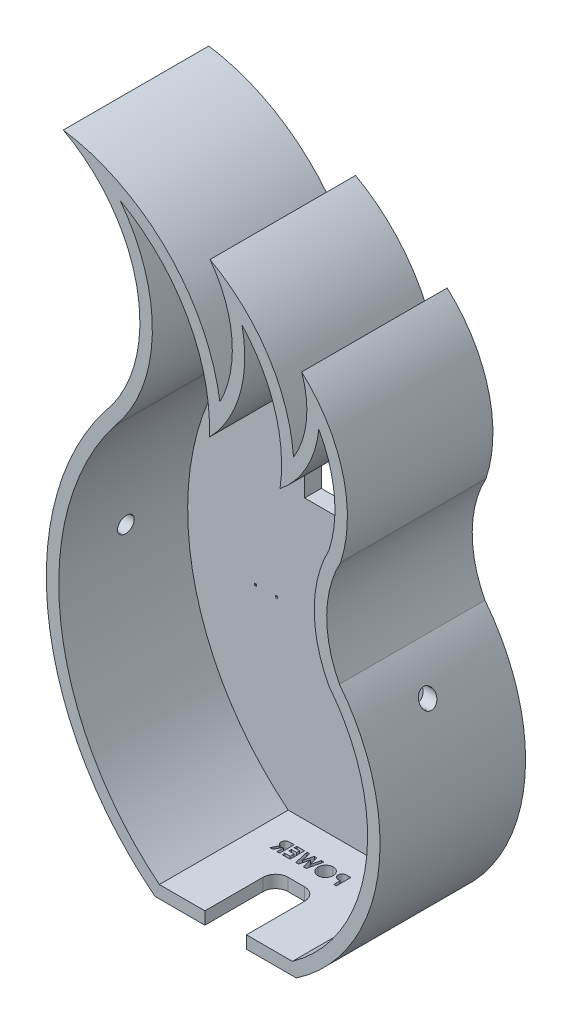
SolidWorks part; units mm, degrees
ref_plane "Plan de face" through (0, 0, 0) normal (0, 0, 1) x (1, 0, 0)
ref_plane "Plan de dessus" through (0, 0, 0) normal (0, 1, 0) x (1, 0, 0)
ref_plane "Plan de droite" through (0, 0, 0) normal (1, 0, 0) x (0, 0, -1)
sketch "Esquisse1" plane through (0, 0, 0) normal (0, 0, 1) x (1, 0, 0)
  line L11 (34.5922, -83.2059) -> (2.5922, -83.2059)
  arc A27 (-8.2284, 6.8779) -> (-6.8432, 54.5989) centre (-37.0902, 31.5963) ccw
  arc A28 (14.6078, 15.9991) -> (-6.8432, 54.5989) centre (-27.3471, 17.9439) ccw
  arc A29 (14.6078, 15.9991) -> (22.4562, 43.331) centre (-6.8587, 36.956) ccw
  arc A30 (31.6225, 13.7941) -> (22.4562, 43.331) centre (-4.0097, 18.927) ccw
  arc A31 (31.6225, 13.7941) -> (40.9447, 30.8086) centre (16.0766, 33.3728) ccw
  arc A32 (43.4046, 6.8505) -> (40.9447, 30.8086) centre (14.6078, 15.9991) ccw
  arc A33 (43.4046, 6.8505) -> (43.3898, -21.4623) centre (69.8471, -7.3198) ccw
  arc A34 (-8.2284, 6.8779) -> (2.5922, -83.2059) centre (43.4002, -32.6124) ccw
  arc A35 (34.5922, -83.2059) -> (43.3898, -21.4623) centre (9.6799, -48.1577) ccw
  point P0 (0, 0)
extrude "Boss.-Extru.1" add sketch "Esquisse1" along normal blind 4
sketch "Esquisse3" plane through (0, 0, 0) normal (0, 0, 1) x (1, 0, 0)
  line L1 (2.5922, -83.2059) -> (34.5922, -83.2059)
  line L2 (2.5922, -83.2059) -> (34.5922, -83.2059)
  line L4 (1.5465, -86.2059) -> (35.5321, -86.2059)
  line L5 (1.5465, -86.2059) -> (35.5321, -86.2059)
  arc A9 (-8.2284, 6.8779) -> (2.5922, -83.2059) centre (43.4002, -32.6124) ccw
  arc A10 (34.5922, -83.2059) -> (43.3898, -21.4623) centre (9.6799, -48.1577) ccw
  arc A11 (43.4046, 6.8505) -> (43.3898, -21.4623) centre (69.8471, -7.3198) ccw
  arc A12 (43.4046, 6.8505) -> (40.9447, 30.8086) centre (14.6078, 15.9991) ccw
  arc A13 (31.6225, 13.7941) -> (40.9447, 30.8086) centre (16.0766, 33.3728) ccw
  arc A14 (31.6225, 13.7941) -> (22.4562, 43.331) centre (-4.0097, 18.927) ccw
  arc A15 (14.6078, 15.9991) -> (22.4562, 43.331) centre (-6.8587, 36.956) ccw
  arc A16 (14.6078, 15.9991) -> (-6.8432, 54.5989) centre (-27.3471, 17.9439) ccw
  arc A17 (-8.2284, 6.8779) -> (-6.8432, 54.5989) centre (-37.0902, 31.5963) ccw
  arc A18 (-8.2284, 6.8779) -> (2.5922, -83.2059) centre (43.4002, -32.6124) ccw
  arc A19 (34.5922, -83.2059) -> (43.3898, -21.4623) centre (9.6799, -48.1577) ccw
  arc A20 (43.4046, 6.8505) -> (43.3898, -21.4623) centre (69.8471, -7.3198) ccw
  arc A21 (43.4046, 6.8505) -> (40.9447, 30.8086) centre (14.6078, 15.9991) ccw
  arc A22 (31.6225, 13.7941) -> (40.9447, 30.8086) centre (16.0766, 33.3728) ccw
  arc A23 (31.6225, 13.7941) -> (22.4562, 43.331) centre (-4.0097, 18.927) ccw
  arc A24 (14.6078, 15.9991) -> (22.4562, 43.331) centre (-6.8587, 36.956) ccw
  arc A25 (14.6078, 15.9991) -> (-6.8432, 54.5989) centre (-27.3471, 17.9439) ccw
  arc A26 (-8.2284, 6.8779) -> (-6.8432, 54.5989) centre (-37.0902, 31.5963) ccw
  arc A36 (-10.5593, 8.7685) -> (1.5465, -86.2059) centre (43.4002, -32.6124) ccw
  arc A37 (35.5321, -86.2059) -> (45.9152, -19.8204) centre (9.6799, -48.1577) ccw
  arc A38 (46.1745, 5.6651) -> (45.9152, -19.8204) centre (69.8471, -7.3198) ccw
  arc A39 (46.1745, 5.6651) -> (36.8236, 40.6913) centre (14.6078, 15.9991) ccw
  arc A40 (34.8736, 21.9416) -> (36.8236, 40.6913) centre (16.0766, 33.3728) ccw
  arc A41 (34.8736, 21.9416) -> (14.7826, 53.1008) centre (-4.0097, 18.927) ccw
  arc A42 (17.1557, 24.6146) -> (14.7826, 53.1008) centre (-6.8587, 36.956) ccw
  arc A43 (17.1557, 24.6146) -> (-20.514, 62.4221) centre (-27.3471, 17.9439) ccw
  arc A44 (-10.5593, 8.7685) -> (-20.514, 62.4221) centre (-37.0902, 31.5963) ccw
  arc A45 (-10.5593, 8.7685) -> (1.5465, -86.2059) centre (43.4002, -32.6124) ccw
  arc A46 (35.5321, -86.2059) -> (45.9152, -19.8204) centre (9.6799, -48.1577) ccw
  arc A47 (46.1745, 5.6651) -> (45.9152, -19.8204) centre (69.8471, -7.3198) ccw
  arc A48 (46.1745, 5.6651) -> (36.8236, 40.6913) centre (14.6078, 15.9991) ccw
  arc A49 (34.8736, 21.9416) -> (36.8236, 40.6913) centre (16.0766, 33.3728) ccw
  arc A50 (34.8736, 21.9416) -> (14.7826, 53.1008) centre (-4.0097, 18.927) ccw
  arc A51 (17.1557, 24.6146) -> (14.7826, 53.1008) centre (-6.8587, 36.956) ccw
  arc A52 (17.1557, 24.6146) -> (-20.514, 62.4221) centre (-27.3471, 17.9439) ccw
  arc A53 (-10.5593, 8.7685) -> (-20.514, 62.4221) centre (-37.0902, 31.5963) ccw
  dimension "D1" = 0
  dimension "D2" = 3
extrude "Boss.-Extru.4" add sketch "Esquisse3" along normal blind 35
sketch "Esquisse4" plane through (0, 0, 0) normal (1, 0, 0) x (0, 0, -1)
  spline S0 degree 3 poles (-21, -27.9419) (-21, -28.3379) (-20.9871, -28.4677) (-20.9363, -28.7231) (-20.8979, -28.8501) (-20.7976, -29.0923) (-20.7362, -29.2072) (-20.5911, -29.4247) (-20.5066, -29.5277) (-20.2296, -29.8047) (-20.0063, -29.9538) (-19.5244, -30.1534) (-19.2609, -30.2059) (-18.8691, -30.2059) (-18.7365, -30.1928) (-18.4797, -30.1414) (-18.3549, -30.1035) (-18.1126, -30.003) (-17.9954, -29.9402) (-17.7787, -29.795) (-17.6777, -29.7122) (-17.491, -29.5251) (-17.4082, -29.4238) (-17.2636, -29.2069) (-17.2012, -29.0899) (-17.1012, -28.8474) (-17.0635, -28.7228) (-17.0128, -28.4666) (-16.9999, -28.3341) (-17.0003, -27.9431) (-17.0528, -27.6804) (-17.252, -27.1998) (-17.4008, -26.9769) (-17.677, -26.7004) (-17.7797, -26.6159) (-17.9972, -26.4705) (-18.112, -26.409) (-18.354, -26.3086) (-18.4813, -26.2699) (-18.7373, -26.2189) (-18.8672, -26.2059) (-19.1313, -26.2058) (-19.262, -26.2188) (-19.5178, -26.2697) (-19.6446, -26.3081) (-19.8873, -26.4087) (-20.0022, -26.4702) (-20.2194, -26.6152) (-20.3223, -26.6997) (-20.5067, -26.8842) (-20.5894, -26.9848) (-20.7353, -27.2029) (-20.7975, -27.3194) (-20.947, -27.6798) (-21, -27.9419) (-21, -28.3379) (-20.9871, -28.4677) knots -0.0625 -0.0625 0 0 0.03125 0.03125 0.0625 0.0625 0.09375 0.09375 0.125 0.125 0.1875 0.1875 0.25 0.25 0.28125 0.28125 0.3125 0.3125 0.34375 0.34375 0.375 0.375 0.40625 0.40625 0.4375 0.4375 0.46875 0.46875 0.5 0.5 0.5625 0.5625 0.625 0.625 0.65625 0.65625 0.6875 0.6875 0.71875 0.71875 0.75 0.75 0.78125 0.78125 0.8125 0.8125 0.84375 0.84375 0.875 0.875 0.90625 0.90625 0.9375 0.9375 1 1 1.03125 1.03125 1.0625 only from (-21, -28.2059) to (-21, -28.2059) construction
  spline S1 degree 3 poles (-21, -27.9419) (-21, -28.3379) (-20.9871, -28.4677) (-20.9363, -28.7231) (-20.8979, -28.8501) (-20.7976, -29.0923) (-20.7362, -29.2072) (-20.5911, -29.4247) (-20.5066, -29.5277) (-20.2296, -29.8047) (-20.0063, -29.9538) (-19.5244, -30.1534) (-19.2609, -30.2059) (-18.8691, -30.2059) (-18.7365, -30.1928) (-18.4797, -30.1414) (-18.3549, -30.1035) (-18.1126, -30.003) (-17.9954, -29.9402) (-17.7787, -29.795) (-17.6777, -29.7122) (-17.491, -29.5251) (-17.4082, -29.4238) (-17.2636, -29.2069) (-17.2012, -29.0899) (-17.1012, -28.8474) (-17.0635, -28.7228) (-17.0128, -28.4666) (-16.9999, -28.3341) (-17.0003, -27.9431) (-17.0528, -27.6804) (-17.252, -27.1998) (-17.4008, -26.9769) (-17.677, -26.7004) (-17.7797, -26.6159) (-17.9972, -26.4705) (-18.112, -26.409) (-18.354, -26.3086) (-18.4813, -26.2699) (-18.7373, -26.2189) (-18.8672, -26.2059) (-19.1313, -26.2058) (-19.262, -26.2188) (-19.5178, -26.2697) (-19.6446, -26.3081) (-19.8873, -26.4087) (-20.0022, -26.4702) (-20.2194, -26.6152) (-20.3223, -26.6997) (-20.5067, -26.8842) (-20.5894, -26.9848) (-20.7353, -27.2029) (-20.7975, -27.3194) (-20.947, -27.6798) (-21, -27.9419) (-21, -28.3379) (-20.9871, -28.4677) knots -0.0625 -0.0625 0 0 0.03125 0.03125 0.0625 0.0625 0.09375 0.09375 0.125 0.125 0.1875 0.1875 0.25 0.25 0.28125 0.28125 0.3125 0.3125 0.34375 0.34375 0.375 0.375 0.40625 0.40625 0.4375 0.4375 0.46875 0.46875 0.5 0.5 0.5625 0.5625 0.625 0.625 0.65625 0.65625 0.6875 0.6875 0.71875 0.71875 0.75 0.75 0.78125 0.78125 0.8125 0.8125 0.84375 0.84375 0.875 0.875 0.90625 0.90625 0.9375 0.9375 1 1 1.03125 1.03125 1.0625 only from (-21, -28.2059) to (-21, -28.2059)
extrude "Enlèv. mat.-Extru.1" cut sketch "Esquisse4" against normal through all both and the other way through all
sketch "Esquisse5" plane through (0, -86.2059, 0) normal (0, -1, 0) x (1, 0, 0)
  line L0 (18.5393, 35) -> (18.5393, -24.4468) construction
  line L1 (1.5465, 35) -> (35.5321, 35) construction
  line L2 (13.5393, 35) -> (13.5393, 21)
  line L3 (16.5393, 18) -> (20.5393, 18)
  line L4 (23.5393, 21) -> (23.5393, 35)
  line L5 (23.5393, 35) -> (13.5393, 35)
  line L6 (24.5667, 14) -> (-4.0878, 14) construction
  arc A0 (20.5393, 18) -> (23.5393, 21) centre (20.5393, 21) ccw
  arc A1 (13.5393, 21) -> (16.5393, 18) centre (16.5393, 21) ccw
  text T0 "<b>POWER</b>"
  point P4 (21.8203, 1.5314)
  point P13 (13.5393, 18)
  point P15 (24.5667, 14)
  dimension "D3" = 3
  dimension "D1" = 17
  dimension "D2" = 10
  dimension "D4" = 4
extrude "Enlèv. mat.-Extru.2" cut sketch "Esquisse5" against normal up to next body kept at (-10.5593, 8.7685, 0)
sketch "Esquisse6" plane through (0, 0, 0) normal (0, 0, 1) x (1, 0, 0)
  line L0 (18.5393, -86.2059) -> (18.5393, 61.4011) construction
  line L1 (1.5465, -86.2059) -> (35.5321, -86.2059) construction
  line L2 (6.5393, -1.2059) -> (30.5393, -1.2059)
  line L3 (30.5393, -1.2059) -> (30.5393, -16.2059)
  line L4 (30.5393, -16.2059) -> (6.5393, -16.2059)
  line L5 (6.5393, -1.2059) -> (6.5393, -16.2059)
  line L6 (38.5393, -40.2059) -> (-54.3097, -40.2059) construction
  line L12 (-0.5028, -40.2059) -> (-5.0028, -40.2059) construction
  line L20 (-0.5028, -40.4559) -> (-0.0028, -40.4559)
  line L21 (-0.0028, -40.4559) -> (-0.0028, -39.9559)
  line L22 (-0.0028, -39.9559) -> (-0.5028, -39.9559)
  line L23 (-0.5028, -39.9559) -> (-0.5028, -40.4559)
  line L24 (-5.0028, -39.9559) -> (-5.5028, -39.9559)
  line L25 (-5.5028, -39.9559) -> (-5.5028, -40.4559)
  line L26 (-5.5028, -40.4559) -> (-5.0028, -40.4559)
  line L27 (-5.0028, -40.4559) -> (-5.0028, -39.9559)
  circle A0 centre (18.5393, 2.7941) radius 1.5 construction
  circle A1 centre (18.5393, 2.7941) radius 1.5
  circle A2 centre (18.5393, -20.2059) radius 1.5 construction
  circle A3 centre (18.5393, -20.2059) radius 1.5
  circle A4 centre (38.5393, -40.2059) radius 2.5
  point P9 (18.5393, -16.2059)
  point P10 (18.5393, -1.2059)
  point P35 (-0.0028, -40.2059)
  dimension "D5" = 5
  dimension "D1" = 24
  dimension "D2" = 15
  dimension "D3" = 70
  dimension "D4" = 20
  dimension "D6" = 46
  dimension "D7" = 4.5
  dimension "D8" = 0.5
extrude "Enlèv. mat.-Extru.3" cut sketch "Esquisse6" along normal through all
sketch "Esquisse7" plane through (0, 0, 0) normal (0, 0, -1) x (-1, 0, 0)
  line L0 (0.5028, -40.2059) -> (5.0028, -40.2059) construction
  line L1 (0.5028, -39.9559) -> (0.5028, -40.4559) construction
  line L2 (5.0028, -40.4559) -> (5.0028, -39.9559) construction
  line L3 (2.7528, -47.7059) -> (2.7528, -52.7059)
  line L4 (2.7528, -52.7059) -> (4.2528, -52.7059)
  line L5 (4.2528, -52.7059) -> (6.7528, -55.2059)
  line L6 (6.7528, -55.2059) -> (6.7528, -45.2059)
  line L7 (6.7528, -50.2059) -> (-6.2198, -50.2059) construction
  line L8 (2.7528, -47.7059) -> (4.2528, -47.7059)
  line L9 (4.2528, -47.7059) -> (6.7528, -45.2059)
  line L10 (6.7528, -50.2059) -> (15.7258, -45.2059) construction
  line L11 (6.7528, -50.2059) -> (15.7258, -55.2059) construction
  line L12 (10.391, -48.1785) -> (11.3306, -47.655)
  line L13 (12.3974, -47.0605) -> (13.9767, -46.1805)
  line L14 (10.391, -52.2332) -> (11.3306, -52.7567)
  line L15 (12.3974, -53.3512) -> (13.9767, -54.2312)
  line L40 (-18.5393, -96.9714) -> (-18.5393, 16.2783) construction
  line L41 (-26.5393, -80.2059) -> (-10.5393, -80.2059)
  line L42 (-10.5393, -80.2059) -> (-10.5393, -75.2059)
  line L43 (-10.5393, -75.2059) -> (-4.5393, -75.2059)
  line L44 (-4.5393, -75.2059) -> (-18.5393, -65.2059)
  line L45 (-1.5465, -86.2059) -> (-35.5321, -86.2059) construction
  line L46 (-26.5393, -80.2059) -> (-26.5393, -75.2059)
  line L47 (-26.5393, -75.2059) -> (-32.5393, -75.2059)
  line L48 (-32.5393, -75.2059) -> (-18.5393, -65.2059)
  line L58 (-10.6674, -68.9853) -> (-6.6674, -68.9853)
  line L59 (-10.6674, -68.9853) -> (-10.6674, -64.9853)
  line L60 (-5.6674, -68.9853) -> (-4.6674, -68.9853)
  line L61 (-10.6674, -63.9853) -> (-10.6674, -62.9853)
  line L62 (-3.6674, -68.9853) -> (-2.6674, -68.9853)
  line L63 (-10.6674, -61.9853) -> (-10.6674, -60.9853)
  line L64 (-1.6674, -68.9853) -> (-0.6674, -68.9853)
  line L65 (-10.6674, -59.9853) -> (-10.6674, -58.9853)
  circle A1 centre (2.7528, -40.2059) radius 5
  arc A2 (10.391, -52.2332) -> (10.391, -48.1785) centre (8.9282, -50.2059) ccw
  arc A3 (11.3306, -52.7567) -> (11.3306, -47.655) centre (8.9282, -50.2059) ccw
  arc A4 (12.3974, -53.3512) -> (12.3974, -47.0605) centre (8.9282, -50.2059) ccw
  arc A5 (13.9767, -54.2312) -> (13.9767, -46.1805) centre (8.9282, -50.2059) ccw
  arc A11 (-0.6674, -68.9853) -> (-10.6674, -58.9853) centre (-10.6674, -68.9853) ccw
  arc A12 (-1.6674, -68.9853) -> (-10.6674, -59.9853) centre (-10.6674, -68.9853) ccw
  arc A13 (-2.6674, -68.9853) -> (-10.6674, -60.9853) centre (-10.6674, -68.9853) ccw
  arc A14 (-3.6674, -68.9853) -> (-10.6674, -61.9853) centre (-10.6674, -68.9853) ccw
  arc A15 (-4.6674, -68.9853) -> (-10.6674, -62.9853) centre (-10.6674, -68.9853) ccw
  arc A16 (-5.6674, -68.9853) -> (-10.6674, -63.9853) centre (-10.6674, -68.9853) ccw
  arc A17 (-6.6674, -68.9853) -> (-10.6674, -64.9853) centre (-10.6674, -68.9853) ccw
  point P17 (2.7528, -50.2059)
  point P54 (-38.5393, -40.2059)
  point P64 (-18.5393, -80.2059)
  point P67 (-8.6331, -70.4384)
  point P68 (-12.7018, -67.5322)
  point P69 (-10.6674, -68.9853)
  point P70 (-7.8194, -71.0196)
  point P71 (-13.5155, -66.9509)
  point P72 (-10.6674, -68.9853)
  point P73 (-7.0056, -71.6008)
  point P74 (-14.3292, -66.3697)
  point P75 (-10.6674, -68.9853)
  point P76 (-6.1919, -72.1821)
  point P77 (-15.143, -65.7885)
  point P78 (-10.6674, -68.9853)
  point P79 (-5.3782, -72.7633)
  point P80 (-15.9567, -65.2072)
  dimension "D1" = 10
  dimension "D14" = 1
  dimension "D2" = 10
  dimension "D3" = 5
  dimension "D4" = 10
  dimension "D5" = 4
  dimension "D6" = 1.5
  dimension "D8" = 8
  dimension "D9" = 5
  dimension "D10" = 6
  dimension "D11" = 6
  dimension "D12" = 15
  dimension "D13" = 10
  dimension "D15" = 1
  dimension "D16" = 1
  dimension "D17" = 1
  dimension "D18" = 1
  dimension "D19" = 1
extrude "Enlèv. mat.-Extru.4" cut sketch "Esquisse7" against normal blind 1
